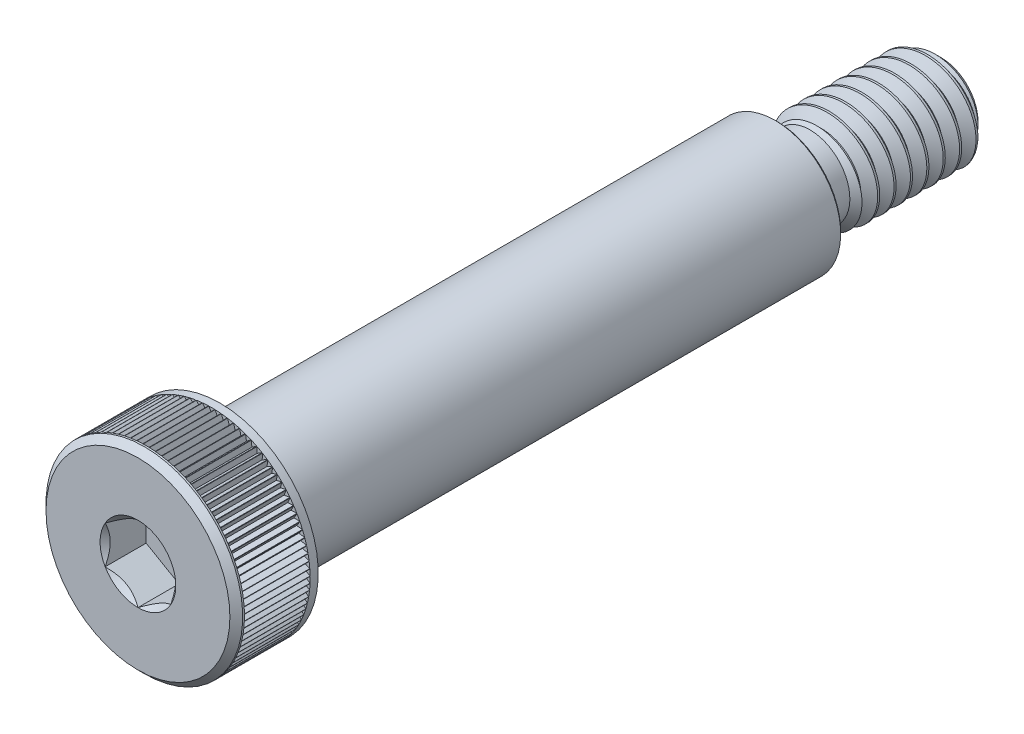
SolidWorks part; units mm, degrees
ref_plane "Front" through (0, 0, 0) normal (0, 0, 1) x (1, 0, 0)
ref_plane "Top" through (0, 0, 0) normal (0, 1, 0) x (1, 0, 0)
ref_plane "Right" through (0, 0, 0) normal (1, 0, 0) x (0, 0, -1)
sketch "Sketch1" plane through (0, 0, 0) normal (1, 0, 0) x (0, 0, -1)
  line L0 (0, 9.525) -> (7.9375, 9.525)
  line L1 (7.9375, 9.525) -> (7.9375, 6.35)
  line L2 (7.9375, 6.35) -> (61.9125, 6.35)
  line L3 (61.9125, 6.35) -> (61.9125, 4.7625)
  line L4 (61.9125, 4.7625) -> (77.7875, 4.7625)
  line L5 (77.7875, 4.7625) -> (77.7875, 0)
  line L6 (77.7875, 0) -> (0, 0)
  line L7 (0, 0) -> (0, 9.525)
  line L8 (0, 9.525) -> (0, -9.525) construction
  line L9 (77.7875, 4.7625) -> (77.7875, -4.7625) construction
  line L10 (61.9125, 6.35) -> (61.9125, -6.35) construction
  line L11 (77.7875, -4.7625) -> (76.1097, -4.7625) construction
  line L12 (34.925, 0) -> (34.925, 6.35) construction
  point P8 (75.4062, -4.7625)
  point P12 (61.9125, 0)
  point P17 (13.335, 6.35)
  point P18 (34.925, 0)
  point P19 (34.925, 6.35)
  point P20 (56.515, 6.35)
  point P21 (56.515, -6.35)
  point P22 (13.335, -6.35)
  dimension "Head Dia" = 19.05
  dimension "Head Ht" = 7.9375
  dimension "Thread Lg" = 15.875
  dimension "Thread Dia" = 9.525
  dimension "Shoulder Dia" = 12.7
  dimension "Shoulder Lg" = 53.975
  dimension "D1" = 2.3813
  dimension "D2" = 1.6778
  dimension "D3" = 26.9875
  dimension "D4" = 5.3975
revolve "Revolve1" add sketch "Sketch1" angle 360 mid plane about L6
ref_plane "Plane1" through (0, 0, -77.7875) normal (0, 0, 1) x (1, 0, 0)
sketch "Sketch3" plane through (0, 0, -77.7875) normal (0, 0, 1) x (1, 0, 0)
  circle A0 centre (0, 0) radius 4.7625
sketch "Sketch5" plane through (0, 0, 0) normal (1, 0, 0) x (0, 0, -1)
  line L0 (61.9125, 6.35) -> (67.5767, 6.35)
  line L1 (67.5767, 6.35) -> (65.0875, 3.8608)
  line L2 (65.0875, 3.8608) -> (62.8142, 3.8608)
  line L3 (61.9125, 6.35) -> (61.9125, 4.7625)
  line L5 (61.9125, 4.7625) -> (77.7875, 4.7625) construction
  line L6 (77.7875, 0) -> (65.0875, 0) construction
  line L7 (71.4375, 0) -> (71.4375, -4.7625) construction
  arc A0 (61.9125, 4.7625) -> (62.8142, 3.8608) centre (62.8142, 4.7625) ccw
  dimension "D1" = 45
  dimension "CADB" = 3.175
  dimension "CADA" = 7.7216
revolve "Cut-Revolve1" cut sketch "Sketch5" angle 360 mid plane about L6
chamfer "Chamfer1" distance 1.1906 angle 45 1 edges at (0, 4.7625, -77.7875)
chamfer "Chamfer2" distance 0.6191 angle 45 1 edges at (0, 9.525, 0)
chamfer "Chamfer3" distance 0.2032 angle 45 1 edges at (0, 6.35, -61.9125)
sketch "Sketch10" plane through (0, 0, 0) normal (1, 0, 0) x (0, 0, -1)
  line L0 (0.6191, 0) -> (7.3184, 0) construction
  line L1 (0.6191, -9.525) -> (0.6191, 9.525) construction
  line L3 (0.6191, 0) -> (0, 0) construction
  line L4 (7.3184, 0) -> (7.9375, 0) construction
  line L5 (7.9375, -9.525) -> (7.9375, 9.525) construction
  point P6 (3.9687, 0)
  dimension "D1" = 6.6992
ref_plane "Plane2" through (0, 0, -3.9687) normal (0, 0, 1) x (1, 0, 0)
sketch "Sketch11" plane through (0, 0, -3.9687) normal (0, 0, 1) x (1, 0, 0)
  line L0 (0, 9.0297) -> (0, 9.525) construction
  line L1 (0, 9.0297) -> (0.286, 9.525)
  line L2 (0, 9.0297) -> (-0.286, 9.525)
  line L3 (-0.286, 9.525) -> (0.286, 9.525)
  line L4 (0, 0) -> (-0.286, 9.525) construction
  line L5 (0.286, 9.525) -> (0, 0) construction
  circle A1 centre (0, 0) radius 9.525 construction
  circle A2 centre (0, 0) radius 9.0297 construction
  circle A3 centre (0, 0) radius 8.9059 construction
  point P3 (0, 0.0018)
  point P8 (2.3908, 0.7309)
  dimension "D1" = 0.4953
  dimension "D2" = 3.439
extrude "Cut-Extrude5" cut sketch "Sketch11" against normal mid plane 6.3643
pattern_circular "CirPattern1" count 99 over 360 about axis through (0, 0, -77.7875) along (0, 0, -1) of "Cut-Extrude5"
sketch "Sketch8" plane through (0, 0, 0) normal (0, 0, 1) x (1, 0, 0)
  line L1 (3.175, 1.8331) -> (0, 3.6662)
  line L2 (0, 3.6662) -> (-3.175, 1.8331)
  line L3 (-3.175, 1.8331) -> (-3.175, -1.8331)
  line L4 (-3.175, -1.8331) -> (0, -3.6662)
  line L5 (0, -3.6662) -> (3.175, -1.8331)
  line L6 (3.175, -1.8331) -> (3.175, 1.8331)
  circle A0 centre (0, 0) radius 3.175 construction
  dimension "Hex" = 6.35
extrude "Cut-Extrude2" cut sketch "Sketch8" against normal blind 3.9688
sketch "Sketch9" plane through (0, 0, 0) normal (0, 0, 1) x (1, 0, 0)
  circle A0 centre (0, 0) radius 3.6662
extrude "Cut-Extrude4" cut sketch "Sketch9" against normal blind 3.9688 draft 45
sketch "Front Sketch" plane through (0, 0, 0) normal (0, 0, 1) x (1, 0, 0)
  line L0 (3.175, -1.8331) -> (3.175, 1.8331) construction
  line L1 (-3.175, 1.8331) -> (-3.175, -1.8331) construction
  circle A0 centre (0, 0) radius 9.525 construction
  point P4 (-3.175, 0)
  point P5 (3.175, 0)
  point P6 (9.525, 0)
  point P9 (-9.525, 0)
ref_plane "Contact Plane 1" through (0, 0, -7.9375) normal (0, 0, -1) x (-1, 0, 0)
ref_axis "Center Axis 1" through (0, 0, -77.7875) along (0, 0, 1)
curve "Helix/Spiral1" pitch 1.5875 height 17.4625 radius 4.7625 centre (0, 0, -77.7875) axis (0, 0, 1) start towards (0, 1, 0)
sketch "Sketch4" plane through (0, 0, 0) normal (1, 0, 0) x (0, 0, -1)
  line L0 (77.6883, 4.9344) -> (79.2758, 4.9344) construction
  line L1 (79.2758, 4.9344) -> (78.482, 3.5595) construction
  line L3 (78.482, 3.5595) -> (77.6883, 4.9344) construction
  line L4 (77.7379, 4.8484) -> (79.2262, 4.8484) construction
  line L5 (77.7875, 4.7625) -> (79.1766, 4.7625) construction
  line L6 (78.3828, 3.7314) -> (78.5812, 3.7314) construction
  line L7 (78.482, 3.7314) -> (78.482, 3.5595) construction
  line L8 (78.482, 4.9344) -> (78.482, 4.7625) construction
  line L9 (77.7379, 4.8484) -> (79.2262, 4.8484)
  line L10 (79.2262, 4.8484) -> (78.5812, 3.7314)
  line L11 (78.5812, 3.7314) -> (78.3828, 3.7314)
  line L12 (78.3828, 3.7314) -> (77.7379, 4.8484)
  point P14 (78.482, 4.8484)
  point P15 (78.482, 4.9344)
  dimension "D1" = 1.5875
  dimension "D2" = 0.1984
sweep "Cut-Sweep1" cut profiles "Sketch4" path "Helix/Spiral1" align with end faces yes
sketch "Sketch12" plane through (0, 0, 0) normal (1, 0, 0) x (0, 0, -1)
  line L1 (61.9125, 6.1468) -> (61.7093, 6.35)
  line L2 (61.7093, 6.35) -> (7.9375, 6.35)
  line L3 (7.9375, 6.35) -> (7.9375, 0)
  line L4 (7.9375, -9.525) -> (7.9375, 9.525) construction
  line L5 (7.9375, 0) -> (61.9125, 0)
  line L6 (61.9125, 6.1468) -> (61.9125, 4.7625)
  line L7 (65.0875, 3.8608) -> (62.8142, 3.8608) construction
  line L8 (65.0875, 3.8608) -> (62.8142, 3.8608)
  line L9 (65.0875, 3.8608) -> (65.0875, 0)
  line L10 (65.0875, 0) -> (61.9125, 0)
  arc A0 (61.9125, 4.7625) -> (62.8142, 3.8608) centre (62.8142, 4.7625) ccw construction
  arc A1 (61.9125, 4.7625) -> (62.8142, 3.8608) centre (62.8142, 4.7625) ccw
revolve "Revolve2" add sketch "Sketch12" angle 360 about L5
equation "\"D3@Helix/Spiral1\" = \"Thread Lg@Sketch1\" + \"D4@Helix/Spiral1\""
equation "\"D1@Chamfer1\" = \"Thread Dia@Sketch1\" * .125"
equation "\"D1@Cut-Extrude2\"= \"Head Ht@Sketch1\" * .5"
equation "\"D1@Cut-Extrude4\" = \"D1@Cut-Extrude2\""
equation "\"D1@Chamfer2\" = \"Head Dia@Sketch1\" * .0325"
equation "\"D1@Sketch1\"=\"D4@Helix/Spiral1\"*1.5"
equation "\"D1@Sketch11\"=\"D1@Chamfer2\"*.8"
equation "\"D1@Cut-Extrude5\"=\"D1@Sketch10\"*.95"
equation "\"D1@CirPattern1\"=(360/\"D2@Sketch11\")-6"
equation "\"D3@Sketch1\"=\"Shoulder Lg@Sketch1\"/2"
equation "\"D4@Sketch1\"=\"D3@Sketch1\"*.2"
equation "\"D1@Sketch4\"=\"D4@Helix/Spiral1\""
equation "\"D2@Sketch4\"=\"D1@Sketch4\"/8"
